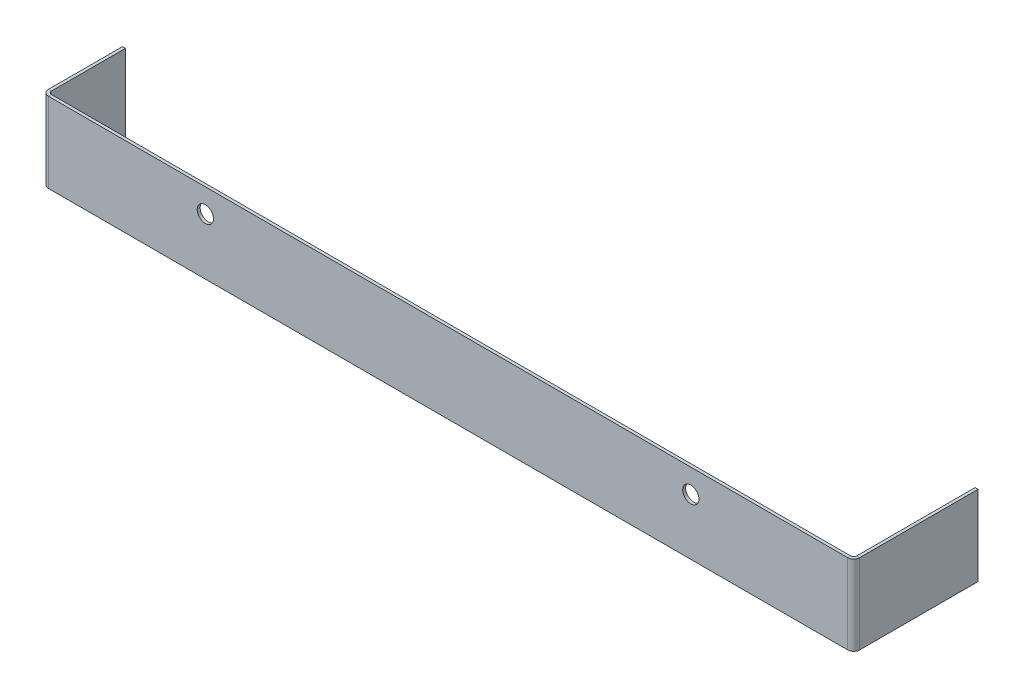
SolidWorks part; units mm, degrees
note: The reader was unsure of these and kept them because the rebuilt part matched: flange length of "Edge-Flange1", "Edge-Flange2".
material "3.3315 (EN-AW 5005)"
ref_plane "Front Plane" through (0, 0, 0) normal (0, 0, 1) x (1, 0, 0)
ref_plane "Top Plane" through (0, 0, 0) normal (0, 1, 0) x (1, 0, 0)
ref_plane "Right Plane" through (0, 0, 0) normal (1, 0, 0) x (0, 0, -1)
sketch "Sketch1" plane through (0, 0, 0) normal (0, 0, 1) x (1, 0, 0)
  line L1 (-135, -13.5) -> (135, -13.5)
  line L2 (-135, -13.5) -> (-135, 13.5)
  line L3 (-135, 13.5) -> (135, 13.5)
  line L4 (135, -13.5) -> (135, 13.5)
  line L5 (-135, -13.5) -> (135, 13.5) construction
  line L6 (-135, 13.5) -> (135, -13.5) construction
  point P0 (0, 0)
  dimension "D1" = 270
  dimension "D2" = 27
base flange "Base-Flange1" sketch "Sketch1" thickness 1 reverse thickness direction no parameters "D1"=4
edge flange "Edge-Flange1" sketch "Sketch8" flange angle 90 flange length 41 flange position bend outside bend radius 1 thickness 1 relief rectangular parameters "D6"=10
sketch "Sketch8" plane through (135, 0, -1) normal (-1, 0, 0) x (0, 1, 0)
  line L2 (-13.5, 0) -> (-13.5, 41)
  line L3 (-13.5, 41) -> (13.5, 41)
  line L4 (13.5, 41) -> (13.5, 0)
  line L5 (13.5, 0) -> (-13.5, 0) construction
  line L6 (13.5, 0) -> (-13.5, 0)
bend "EdgeBend1" bend radius 1 bend angle 90 parameters "D5"=1
edge flange "Edge-Flange2" sketch "Sketch11" flange angle 90 flange length 26 flange position bend outside bend radius 1 thickness 1 relief rectangular parameters "D6"=10
sketch "Sketch11" plane through (-135, 0, -1) normal (1, 0, 0) x (0, -1, 0)
  line L2 (-13.5, 0) -> (-13.5, 26)
  line L3 (-13.5, 26) -> (13.5, 26)
  line L4 (13.5, 26) -> (13.5, 0)
  line L5 (13.5, 0) -> (-13.5, 0) construction
  line L6 (13.5, 0) -> (-13.5, 0)
bend "EdgeBend2" bend radius 1 bend angle 90 parameters "D5"=2
hole_wizard "M5 Clearance Hole1" positions "Sketch12" profile "Sketch13" hole size "M5" standard "ISO" end condition through all
sketch "Sketch12" plane through (0, 0, 0) normal (0, 0, 1) x (1, 0, 0)
  point P0 (82, 5.5)
  point P3 (-82, 5.5)
sketch "Sketch13" plane through (82, 5.5, 0) normal (1, 0, 0) x (0, -1, 0)
  line L0 (0, 0) -> (0, 42)
  line L1 (0, 42) -> (2.75, 42)
  line L2 (2.75, 42) -> (2.75, 0)
  line L5 (2.75, 0) -> (0, 0)
  line L11 (0, -6.35) -> (0, 107.95) construction
  dimension "Thru Hole Dia." = 5.5
  dimension "Thru Hole Depth" = 42
sketch "Bend-Lines1" [suppressed] plane through (0, 0, 0) normal (0, 1, 0) x (1, 0, 0)
sketch "Bounding-Box1" [suppressed] plane through (0, 0, 0) normal (0, 1, 0) x (1, 0, 0)
sheet metal parameters "Sheet-Metal1" thickness 1 parameters "D1"=4
flat pattern "Flat-Pattern1" [suppressed]
sketch "Bend-Lines2" plane through (0, 0, 0) normal (0, 1, 0) x (1, 0, 0)
sketch3d "Bounding-Box2" [suppressed]
  line L0 (135, -7.5, 0) -> (-135, -7.5, 0) construction
  line L1 (135, 7.5, 0) -> (-135, 7.5, 0) construction
  line L2 (135, -7.5, 0) -> (135, 7.5, 0) construction
  line L3 (-135, -7.5, 0) -> (-135, 7.5, 0) construction
sheet metal parameters "Sheet-Metal2" thickness 1 parameters "D1"=4
flat pattern "Flat-Pattern1"
sketch "Bend-Lines2" plane through (0, 0, 0) normal (0, 0, 1) x (1, 0, 0)
  line L0 (136.1781, -13.5) -> (136.1781, 13.5) construction
  line L1 (136.1781, -13.5) -> (136.1781, 13.5) construction
sketch3d "Bounding-Box2" [suppressed]
  line L0 (-135, -13.5, 0) -> (166.3562, -13.5, 0) construction
  line L1 (-135, 13.5, 0) -> (166.3562, 13.5, 0) construction
  line L2 (-135, -13.5, 0) -> (-135, 13.5, 0) construction
  line L3 (166.3562, -13.5, 0) -> (166.3562, 13.5, 0) construction
bend of the flat pattern "Flatten-<EdgeBend1>1"
sheet metal parameters "Sheet-Metal3" thickness 1 parameters "D1"=4
flat pattern "Flat-Pattern1"
sketch "Bend-Lines2" plane through (0, 0, 0) normal (0, 0, 1) x (1, 0, 0)
  line L0 (136.1781, -13.5) -> (136.1781, 13.5) construction
  line L1 (136.1781, -13.5) -> (136.1781, 13.5) construction
  line L2 (-136.1781, 13.5) -> (-136.1781, -13.5) construction
  line L3 (-136.1781, 13.5) -> (-136.1781, -13.5) construction
sketch3d "Bounding-Box2" [suppressed]
  line L0 (-162.3562, -13.5, 0) -> (177.3562, -13.5, 0) construction
  line L1 (-162.3562, 13.5, 0) -> (177.3562, 13.5, 0) construction
  line L2 (-162.3562, -13.5, 0) -> (-162.3562, 13.5, 0) construction
  line L3 (177.3562, -13.5, 0) -> (177.3562, 13.5, 0) construction
bend of the flat pattern "Flatten-<EdgeBend1>1"
bend of the flat pattern "Flatten-<EdgeBend2>1"
sheet metal parameters "Sheet-Metal4" thickness 1 parameters "D1"=4
flat pattern "Flat-Pattern1"
sketch "Bend-Lines2" plane through (0, 0, 0) normal (0, 0, 1) x (1, 0, 0)
  line L0 (136.1781, -13.5) -> (136.1781, 13.5) construction
  line L1 (136.1781, -13.5) -> (136.1781, 13.5) construction
  line L2 (-136.1781, 13.5) -> (-136.1781, -13.5) construction
  line L3 (-136.1781, 13.5) -> (-136.1781, -13.5) construction
sketch3d "Bounding-Box2" [suppressed]
  line L0 (-162.3562, -13.5, 0) -> (177.3562, -13.5, 0) construction
  line L1 (-162.3562, 13.5, 0) -> (177.3562, 13.5, 0) construction
  line L2 (-162.3562, -13.5, 0) -> (-162.3562, 13.5, 0) construction
  line L3 (177.3562, -13.5, 0) -> (177.3562, 13.5, 0) construction
bend of the flat pattern "Flatten-<EdgeBend1>1"
bend of the flat pattern "Flatten-<EdgeBend2>1"
